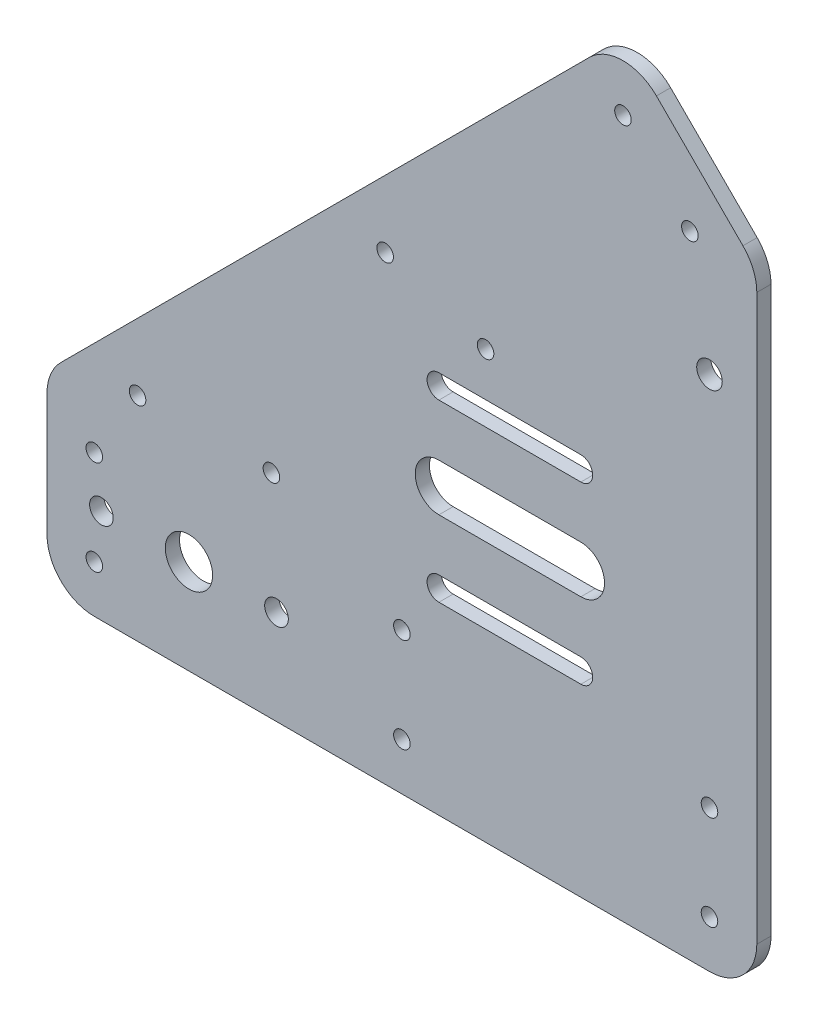
SolidWorks part; units mm, degrees
ref_plane "Front Plane" through (0, 0, 0) normal (0, 0, 1) x (1, 0, 0)
ref_plane "Top Plane" through (0, 0, 0) normal (0, 1, 0) x (1, 0, 0)
ref_plane "Right Plane" through (0, 0, 0) normal (1, 0, 0) x (0, 0, -1)
sketch "Sketch1" plane through (0, 0, 0) normal (0, 0, 1) x (1, 0, 0)
  line L0 (-75, 20) -> (46.7157, 141.7157)
  line L1 (-18.4315, 20) -> (75, 20) construction
  line L2 (-75, 20) -> (-75, -20)
  line L3 (-75, -20) -> (75, -20)
  line L4 (75, 20) -> (75, -20)
  line L5 (-75, 20) -> (75, -20) construction
  line L6 (-75, -20) -> (75, 20) construction
  line L7 (-75, -20) -> (75, -20)
  line L11 (46.7157, 141.7157) -> (75, 113.4315)
  line L12 (75, 113.4315) -> (-18.4315, 20) construction
  line L13 (-75, 0) -> (75, 0) construction
  line L14 (-75, 10) -> (75, 10) construction
  line L15 (-75, -10) -> (75, -10) construction
  line L16 (60.8579, 127.5736) -> (-46.7157, 20) construction
  line L17 (-75, 20) -> (-18.4315, 20) construction
  line L18 (53.7868, 134.6447) -> (-60.8579, 20) construction
  line L19 (67.9289, 120.5025) -> (-32.5736, 20) construction
  line L20 (75, 113.4315) -> (75, 20)
  line L21 (46.7157, 127.5736) -> (60.8579, 113.4315) construction
  line L22 (65, -10) -> (65, 10) construction
  line L23 (-65, -10) -> (-65, 10) construction
  line L24 (7.8202, 40) -> (37.8202, 40) construction
  line L25 (7.8202, 45) -> (37.8202, 45)
  line L26 (7.8202, 35) -> (37.8202, 35)
  line L27 (65, 10) -> (65, 103.4315) construction
  line L28 (7.8202, 45) -> (7.8202, 58.5) construction
  line L29 (7.8202, 21.5) -> (37.8202, 21.5) construction
  line L30 (7.8202, 24) -> (37.8202, 24)
  line L31 (7.8202, 21.5) -> (7.8202, 35) construction
  line L32 (22.8202, 35) -> (22.8202, 45) construction
  line L33 (7.8202, 58.5) -> (37.8202, 58.5) construction
  line L34 (7.8202, 61) -> (37.8202, 61)
  line L35 (7.8202, 56) -> (37.8202, 56)
  line L36 (7.8202, 19) -> (37.8202, 19)
  line L37 (-63.5, 0) -> (-26.5, 0) construction
  line L38 (37.8202, 58.5) -> (37.8202, 21.5) construction
  line L39 (-63.5, 2.5) -> (-63.5, -2.5) construction
  line L40 (-26.5, 2.5) -> (-26.5, -2.5) construction
  line L41 (-45, 5) -> (-45, -5) construction
  line L42 (0, 20) -> (0, -20) construction
  line L43 (-10.6066, 84.3934) -> (17.6777, 56.1091) construction
  line L44 (24.7487, 63.1802) -> (-3.5355, 91.4645) construction
  line L45 (-55.8579, 25) -> (-62.9289, 32.0711) construction
  line L46 (-27.5736, 25) -> (-48.7868, 46.2132) construction
  line L47 (46.7157, 127.5736) -> (60.8579, 113.4315) construction
  line L48 (65, 89.2893) -> (75, 89.2893) construction
  line L49 (-65, -20) -> (-65, 20) construction
  circle A0 centre (-45, 0) radius 5
  circle A1 centre (22.8202, 40) radius 5 construction
  circle A2 centre (-65, -10) radius 1.75
  circle A3 centre (0, 10) radius 1.75
  circle A4 centre (65, -10) radius 1.75
  circle A5 centre (-55.8579, 25) radius 1.75
  circle A6 centre (46.7157, 127.5736) radius 1.75
  circle A8 centre (-27.5736, 25) radius 1.75
  circle A9 centre (60.8579, 113.4315) radius 1.75
  circle A10 centre (22.8202, 40) radius 4 construction
  circle A11 centre (-3.5355, 77.3223) radius 1.75
  circle A12 centre (17.6777, 70.2513) radius 1.75
  circle A13 centre (65, 10) radius 1.75
  circle A14 centre (-65, 10) radius 1.75
  circle A15 centre (0, -10) radius 1.75
  arc A16 (7.8202, 45) -> (7.8202, 35) centre (7.8202, 40) ccw
  arc A17 (37.8202, 35) -> (37.8202, 45) centre (37.8202, 40) ccw
  circle A18 centre (65, 89.2893) radius 2.7
  circle A19 centre (7.8202, 58.5) radius 2.5 construction
  circle A21 centre (7.8202, 21.5) radius 2.5 construction
  circle A22 centre (37.8202, 21.5) radius 2.5 construction
  circle A23 centre (37.8202, 58.5) radius 2.5 construction
  arc A26 (7.8202, 61) -> (7.8202, 56) centre (7.8202, 58.5) ccw
  arc A27 (37.8202, 56) -> (37.8202, 61) centre (37.8202, 58.5) ccw
  arc A28 (7.8202, 24) -> (7.8202, 19) centre (7.8202, 21.5) ccw
  arc A29 (37.8202, 19) -> (37.8202, 24) centre (37.8202, 21.5) ccw
  circle A31 centre (-63.5, 0) radius 2.5
  circle A32 centre (-26.5, 0) radius 2.5
  point P0 (0, 0)
  point P50 (22.8202, 40)
  point P63 (22.8202, 21.5)
  point P81 (22.8202, 58.5)
  dimension "D8" = 10
  dimension "D11" = 10
  dimension "D12" = 3.5
  dimension "D17" = 30
  dimension "D18" = 5.4
  dimension "D22" = 5
  dimension "D23" = 2.5
  dimension "D24" = 5
  dimension "D21" = 2.5
  dimension "D26" = 5
  dimension "D27" = 5
  dimension "D1" = 40
  dimension "D2" = 40
  dimension "D3" = 45
  dimension "D4" = 10
  dimension "D5" = 10
  dimension "D6" = 10
  dimension "D7" = 10
  dimension "D9" = 30
  dimension "D10" = 150
  dimension "D13" = 10
  dimension "D14" = 10
  dimension "D15" = 5
  dimension "D16" = 10
  dimension "D19" = 10
  dimension "D20" = 37
  dimension "D28" = 37
  dimension "D29" = 18.5
extrude "Boss-Extrude1" add sketch "Sketch1" along normal blind 3 contours L20 L11 L0 L2 L3 L4 A0 region at (-12.5825, 79.2982, 0)
fillet "Fillet1" radius 10 5 edges at (75, -20, 1.5) (-75, -20, 1.5) (46.7157, 141.7157, 1.5) (75, 113.4315, 1.5) (-75, 20, 1.5)
